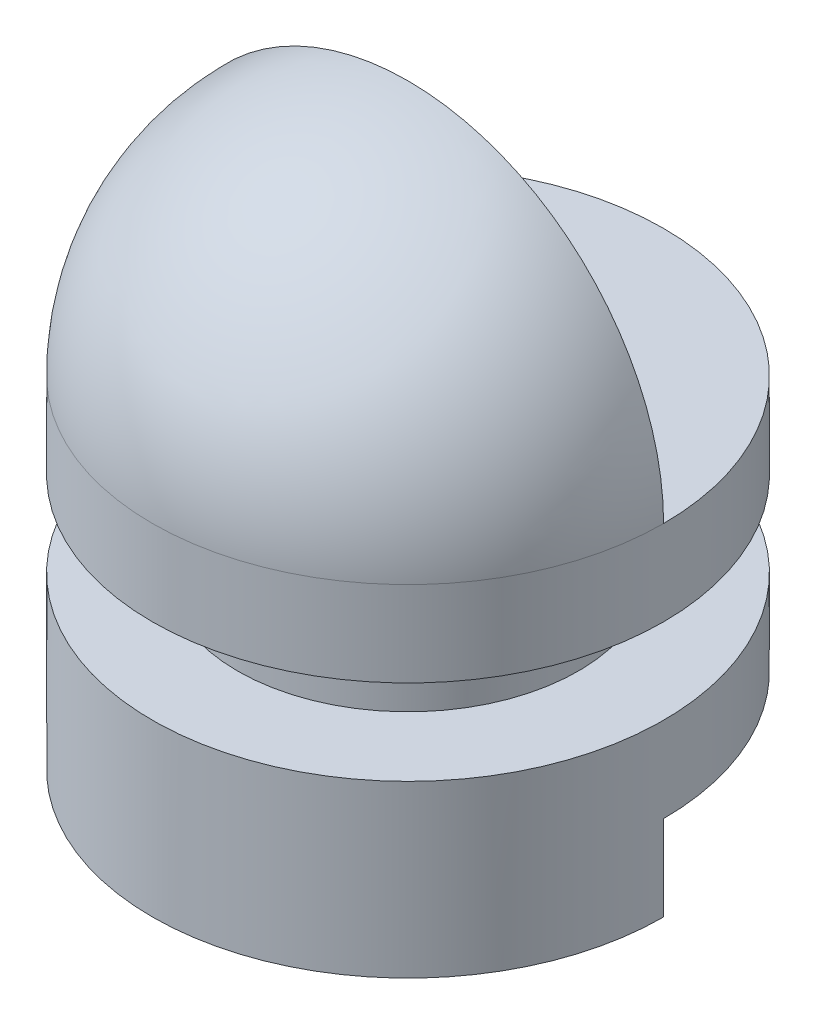
SolidWorks part; units mm, degrees
ref_plane "Front Plane" through (0, 0, 0) normal (0, 0, 1) x (1, 0, 0)
ref_plane "Top Plane" through (0, 0, 0) normal (0, 1, 0) x (1, 0, 0)
ref_plane "Right Plane" through (0, 0, 0) normal (1, 0, 0) x (0, 0, -1)
sketch "Sketch1" plane through (0, 0, 0) normal (0, 1, 0) x (1, 0, 0)
  circle A0 centre (0, 0) radius 20
extrude "Boss-Extrude1" add sketch "Sketch1" along normal blind 10
sketch "Sketch2" plane through (0, 10, 0) normal (0, 1, 0) x (1, 0, 0)
  circle A0 centre (0, 0) radius 30
extrude "Boss-Extrude2" add sketch "Sketch2" along normal blind 10
sketch "Sketch3" plane through (0, 0, 0) normal (0, -1, 0) x (1, 0, 0)
  circle A0 centre (0, 0) radius 30
extrude "Boss-Extrude3" add sketch "Sketch3" along normal blind 10
sketch "Sketch6" plane through (0, 20, 0) normal (0, 1, 0) x (1, 0, 0)
  line L3 (0, 0) -> (-30, 0)
  line L5 (0, 0) -> (0, -30)
  circle A0 centre (0, 0) radius 30 construction
  arc A1 (-30, 0) -> (0, -30) centre (0, 0) ccw
sketch "Sketch8" plane through (0, -10, 0) normal (0, -1, 0) x (-1, 0, 0)
  line L0 (0, 0) -> (30, 0) construction
  line L1 (0, 0) -> (-30, 0)
  line L2 (0, 0) -> (30, 0)
  arc A0 (-30, 0) -> (30, 0) centre (0, 0) ccw
extrude "Boss-Extrude6" add sketch "Sketch8" along normal blind 10
revolve "Revolve3" add sketch "Sketch6" angle 180 about L5 reverse direction yes
